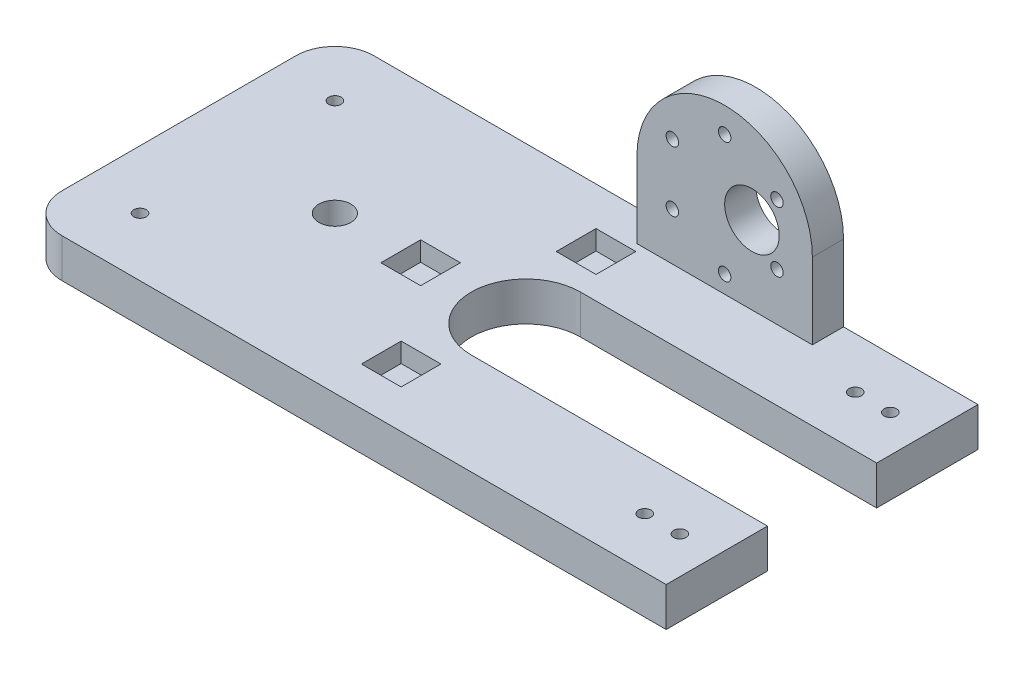
SolidWorks part; units mm, degrees
ref_plane "正面" through (0, 0, 0) normal (0, 0, 1) x (1, 0, 0)
ref_plane "平面" through (0, 0, 0) normal (0, 1, 0) x (1, 0, 0)
ref_plane "右側面" through (0, 0, 0) normal (1, 0, 0) x (0, 0, -1)
sketch "ｽｹｯﾁ1" plane through (0, 0, 0) normal (0, 1, 0) x (1, 0, 0)
  line L0 (82.5, 14) -> (82.5, 40)
  line L1 (-82.5, -40) -> (82.5, -40)
  line L2 (-82.5, -40) -> (-82.5, 40)
  line L3 (-82.5, 40) -> (82.5, 40)
  line L4 (82.5, -40) -> (82.5, -14)
  line L5 (-82.5, -40) -> (82.5, 40) construction
  line L6 (-82.5, 40) -> (82.5, -40) construction
  line L7 (82.5, 14) -> (-7.5, 14)
  line L9 (82.5, -14) -> (-7.5, -14)
  line L10 (-7.5, 14) -> (-7.5, -14)
  line L11 (-82.5, 40) -> (35272.8391, -35315.3391) construction
  line L12 (-82.5, -40) -> (35272.8391, 35315.3391) construction
  circle A0 centre (-42.5, 0) radius 4.1
  point P0 (0, 0)
  point P17 (-42.5, 0)
  dimension "D5" = 8.2
  dimension "D1" = 80
  dimension "D2" = 75
  dimension "D3" = 28
  dimension "D4" = 90
  dimension "D6" = 45
  dimension "D7" = 45
extrude "ﾎﾞｽ - 押し出し1" add sketch "ｽｹｯﾁ1" along normal blind 10
sketch "ｽｹｯﾁ2" plane through (0, 10, 0) normal (0, 1, 0) x (1, 0, 0)
  line L2 (-82.5, 40) -> (-2.5, -40) construction
  line L4 (82.5, 40) -> (-82.5, 40) construction
  circle A0 centre (-67.5, 25) radius 1.6
  circle A3 centre (-67.5, -25) radius 1.6
  dimension "D1" = 3.2
  dimension "D3" = 50
  dimension "D4" = 25
  dimension "D5" = 45
fillet "ﾌｨﾚｯﾄ1" radius 10 2 edges at (-82.5, 5, -40) (-82.5, 5, 40)
fillet "ﾌｨﾚｯﾄ2" 2 edges at (-7.5, 5, 14) (-7.5, 5, -14) type full round first side face at (37.5, 5, 14) second side face at (37.5, 5, -14) middle face at (-7.5, 5, 0)
sketch "ｽｹｯﾁ5" plane through (0, 10, 0) normal (0, 1, 0) x (1, 0, 0)
  line L0 (82.5, 40) -> (-72.5, 40) construction
  line L1 (48, 32) -> (3, 32)
  line L2 (48, 32) -> (48, 40)
  line L3 (48, 40) -> (3, 40)
  line L4 (3, 32) -> (3, 40)
  line L5 (3, 40) -> (48, 32) construction
  line L7 (3, 32) -> (48, 40) construction
  arc A1 (6.5, 14) -> (6.5, -14) centre (6.5, 0) ccw construction
  point P4 (25.5, 36)
  dimension "D1" = 19
  dimension "D2" = 45
  dimension "D3" = 8
extrude "ﾎﾞｽ - 押し出し4" add sketch "ｽｹｯﾁ5" along normal blind 42
fillet "ﾌｨﾚｯﾄ3" 2 edges at (48, 52, -36) (3, 52, -36) type full round first side face at (48, 31, -36) second side face at (3, 31, -36) middle face at (25.5, 52, -36)
sketch "ｽｹｯﾁ6" plane through (0, 0, -32) normal (0, 0, 1) x (1, 0, 0)
  line L0 (-38.4, 10) -> (-46.6, 10) construction
  circle A0 centre (32.5, 30) radius 7
  circle A2 centre (25.5, 45.5) radius 1.6
  circle A3 centre (25.5, 30) radius 15.5 construction
  circle A5 centre (38.9234, 37.75) radius 1.6
  circle A6 centre (38.9234, 22.25) radius 1.6
  circle A7 centre (25.5, 14.5) radius 1.6
  circle A8 centre (12.0766, 22.25) radius 1.6
  circle A9 centre (12.0766, 37.75) radius 1.6
  point P10 (0, 0)
  point P21 (25.5, 30)
  dimension "D2" = 14
  dimension "D3" = 6
  dimension "D5" = 31
  dimension "D1" = 3.2
  dimension "D4" = 20
  dimension "D6" = 7
  dimension "D7" = 70.9
extrude "ｶｯﾄ - 押し出し1" cut sketch "ｽｹｯﾁ6" against normal through all
sketch "ｽｹｯﾁ7" plane through (0, 10, 0) normal (0, 1, 0) x (1, 0, 0)
  line L1 (-5.6, 30.1) -> (4.6, 30.1)
  line L2 (-5.6, 30.1) -> (-5.6, 19.9)
  line L3 (-5.6, 19.9) -> (4.6, 19.9)
  line L4 (4.6, 30.1) -> (4.6, 19.9)
  line L5 (-5.6, 30.1) -> (4.6, 19.9) construction
  line L6 (-5.6, 19.9) -> (4.6, 30.1) construction
  line L7 (-5.6, -19.9) -> (4.6, -19.9)
  line L8 (-5.6, -19.9) -> (-5.6, -30.1)
  line L9 (-5.6, -30.1) -> (4.6, -30.1)
  line L10 (4.6, -19.9) -> (4.6, -30.1)
  line L11 (-5.6, -19.9) -> (4.6, -30.1) construction
  line L12 (-5.6, -30.1) -> (4.6, -19.9) construction
  line L13 (-25.6, -5.1) -> (-15.4, -5.1)
  line L14 (-25.6, -5.1) -> (-25.6, 5.1)
  line L15 (-25.6, 5.1) -> (-15.4, 5.1)
  line L16 (-15.4, -5.1) -> (-15.4, 5.1)
  line L17 (-25.6, -5.1) -> (-15.4, 5.1) construction
  line L18 (-25.6, 5.1) -> (-15.4, -5.1) construction
  circle A0 centre (-42.5, 0) radius 4.1 construction
  point P0 (-0.5, 25)
  point P4 (-0.5, -25)
  point P12 (-20.5, 0)
  point P18 (0, 0)
  dimension "D1" = 10.2
  dimension "D4" = 42
  dimension "D2" = 25
  dimension "D3" = 25
  dimension "D5" = 20
extrude "ｶｯﾄ - 押し出し2" cut sketch "ｽｹｯﾁ7" against normal blind 5
sketch "ｽｹｯﾁ8" plane through (0, 10, 0) normal (0, 1, 0) x (1, 0, 0)
  line L0 (82.5, 14) -> (82.5, 40) construction
  line L1 (82.5, -40) -> (82.5, -14) construction
  circle A0 centre (73, 27) radius 1.6
  circle A1 centre (64, 27) radius 1.6
  circle A2 centre (64, -27) radius 1.6
  circle A3 centre (73, -27) radius 1.6
  point P8 (82.5, 27)
  point P14 (82.5, -27)
  dimension "D3" = 3.2
  dimension "D4" = 9.5
  dimension "D1" = 9.5
  dimension "D2" = 9
  dimension "D5" = 9
extrude "ｶｯﾄ - 押し出し3" cut sketch "ｽｹｯﾁ8" against normal through all
extrude "ｶｯﾄ - 押し出し5" cut sketch "ｽｹｯﾁ2" against normal through all
